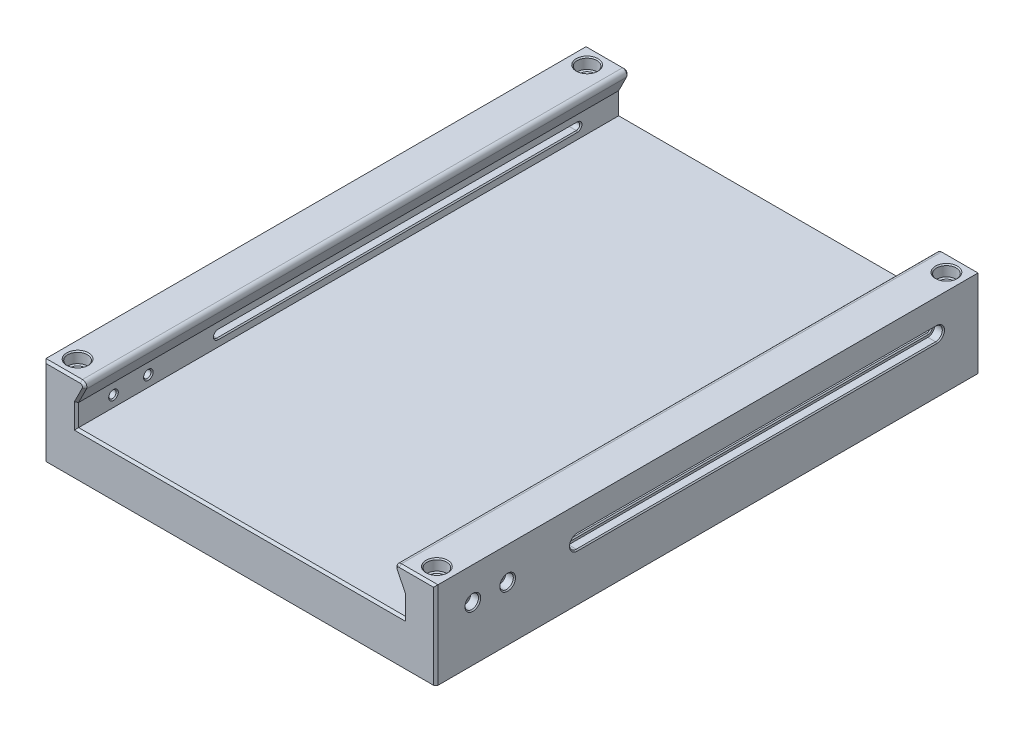
SolidWorks part; units mm, degrees
ref_plane "前视基准面" through (0, 0, 0) normal (0, 0, 1) x (1, 0, 0)
ref_plane "上视基准面" through (0, 0, 0) normal (0, 1, 0) x (1, 0, 0)
ref_plane "右视基准面" through (0, 0, 0) normal (1, 0, 0) x (0, 0, -1)
sketch "草图1" plane through (0, 0, 0) normal (0, 0, 1) x (1, 0, 0)
  line L1 (-90, 10) -> (90, 10)
  line L2 (-90, 10) -> (-90, -10)
  line L3 (-90, -10) -> (90, -10)
  line L4 (90, 10) -> (90, -10)
  line L5 (-90, 10) -> (90, -10) construction
  line L6 (-90, -10) -> (90, 10) construction
  point P0 (0, 0)
  dimension "D1" = 180
  dimension "D2" = 20
extrude "凸台-拉伸1" add sketch "草图1" along normal blind 250
sketch "草图2" plane through (0, 0, 250) normal (0, 0, 1) x (1, 0, 0)
  line L0 (90, 10) -> (-90, 10) construction
  line L1 (-75, 30) -> (-90, 30)
  line L2 (-75, 30) -> (-75, -10)
  line L3 (-75, -10) -> (-90, -10)
  line L4 (-90, 30) -> (-90, -10)
  line L5 (-75, 30) -> (-90, -10) construction
  line L6 (-75, -10) -> (-90, 30) construction
  line L7 (0, 0) -> (0, 83.1513) construction
  line L8 (75, -10) -> (90, 30) construction
  line L9 (75, 30) -> (90, -10) construction
  line L10 (90, 30) -> (90, -10)
  line L11 (75, -10) -> (90, -10)
  line L12 (75, 30) -> (75, -10)
  line L13 (75, 30) -> (90, 30)
  point P0 (-82.5, 10)
  point P15 (82.5, 10)
  dimension "D1" = 15
extrude "凸台-拉伸2" add sketch "草图2" against normal through all
sketch "草图4" plane through (0, 30, 0) normal (0, 1, 0) x (1, 0, 0)
  line L0 (-90, -125) -> (90, -125) construction
  line L1 (-90, 0) -> (-90, -250) construction
  line L2 (90, 0) -> (90, -250) construction
  line L3 (82.5, 0) -> (82.5, -250) construction
  line L4 (90, 0) -> (75, 0) construction
  line L5 (90, -250) -> (75, -250) construction
  line L6 (0, 0) -> (0, -250) construction
  line L7 (75, -250) -> (-75, -250) construction
  circle A30 centre (82.5, -242) radius 2.75
  circle A31 centre (82.5, -8) radius 2.75
  circle A32 centre (-82.5, -242) radius 2.75
  circle A33 centre (-82.5, -8) radius 2.75
  dimension "D1" = 5.5
  dimension "D2" = 8
extrude "切除-拉伸1" cut sketch "草图4" against normal through all
sketch "草图3" plane through (0, 0, 250) normal (0, 0, 1) x (1, 0, 0)
  line L0 (-75, 30) -> (-75, 20)
  line L1 (-75, 10) -> (-75, 30) construction
  line L2 (-75, 20) -> (-70, 30)
  line L3 (-70, 30) -> (-75, 30)
  line L4 (0, 0) -> (0, 81.7607) construction
  line L5 (70, 30) -> (75, 30)
  line L6 (75, 20) -> (70, 30)
  line L7 (75, 30) -> (75, 20)
  dimension "D1" = 5
  dimension "D2" = 10
extrude "凸台-拉伸3" add sketch "草图3" against normal through all
fillet "圆角1" radius 2 2 edges at (70, 30, 125) (-70, 30, 125)
sketch "草图5" plane through (90, 0, 0) normal (1, 0, 0) x (0, 0, -1)
  line L0 (-250, 15) -> (0, 15) construction
  line L1 (-250, -10) -> (-250, 30) construction
  line L2 (0, -10) -> (0, 30) construction
  circle A0 centre (-233, 15) radius 1.7
  circle A1 centre (-217, 15) radius 1.7
  dimension "D3" = 16
  dimension "D4" = 3.4
  dimension "D1" = 5
  dimension "D2" = 17
extrude "切除-拉伸2" cut sketch "草图5" against normal through all
sketch "草图6" plane through (90, 0, 0) normal (1, 0, 0) x (0, 0, -1)
  circle A0 centre (-233, 15) radius 3.1
  circle A1 centre (-217, 15) radius 3.1
  dimension "D1" = 6.2
extrude "切除-拉伸3" cut sketch "草图6" against normal offset from surface (4 mm away) 11 up to face at (75, 15, 234.7)
sketch "草图7" plane through (-90, 0, 0) normal (-1, 0, 0) x (0, 0, 1)
  circle A0 centre (233, 15) radius 3.1
  circle A1 centre (217, 15) radius 3.1
  dimension "D1" = 6.2
extrude "切除-拉伸4" cut sketch "草图7" against normal offset from surface (4 mm away) 11 up to face at (-75, 15, 231.3)
sketch "草图8" plane through (90, 0, 0) normal (1, 0, 0) x (0, 0, -1)
  line L0 (-217, 15) -> (0, 15) construction
  line L1 (0, -10) -> (0, 30) construction
  line L2 (-185, 15) -> (-20, 15) construction
  line L3 (-185, 16.6) -> (-20, 16.6)
  line L4 (-185, 13.4) -> (-20, 13.4)
  arc A0 (-185, 16.6) -> (-185, 13.4) centre (-185, 15) ccw
  arc A1 (-20, 13.4) -> (-20, 16.6) centre (-20, 15) ccw
  point P7 (-102.5, 15)
  dimension "D1" = 3.2
  dimension "D2" = 20
  dimension "D3" = 32
extrude "切除-拉伸5" cut sketch "草图8" against normal through all
sketch "草图9" plane through (90, 0, 0) normal (1, 0, 0) x (0, 0, -1)
  line L0 (-185, 15) -> (-20, 15) construction
  line L1 (-185, 18.1) -> (-20, 18.1)
  line L2 (-185, 11.9) -> (-20, 11.9)
  arc A0 (-185, 18.1) -> (-185, 11.9) centre (-185, 15) ccw
  arc A1 (-20, 11.9) -> (-20, 18.1) centre (-20, 15) ccw
  point P4 (-102.5, 15)
  dimension "D1" = 6.2
extrude "切除-拉伸6" cut sketch "草图9" against normal up to surface (4 mm away) up to face at (86, 15, 220.1)
sketch "草图10" plane through (-90, 0, 0) normal (-1, 0, 0) x (0, 0, 1)
  line L0 (20, 15) -> (185, 15) construction
  line L1 (20, 18.1) -> (185, 18.1)
  line L2 (20, 11.9) -> (185, 11.9)
  arc A0 (20, 18.1) -> (20, 11.9) centre (20, 15) ccw
  arc A1 (185, 11.9) -> (185, 18.1) centre (185, 15) ccw
  point P4 (102.5, 15)
  dimension "D1" = 6.2
extrude "切除-拉伸7" cut sketch "草图10" against normal up to surface (4 mm away) up to face at (-86, 15, 213.9)
sketch "草图11" plane through (0, 30, 0) normal (0, 1, 0) x (1, 0, 0)
  circle A0 centre (-82.5, -8) radius 4.5
  circle A1 centre (82.5, -8) radius 4.5
  circle A2 centre (82.5, -242) radius 4.5
  circle A3 centre (-82.5, -242) radius 4.5
  dimension "D1" = 9
extrude "切除-拉伸8" cut sketch "草图11" against normal blind 5
chamfer "倒角1" distance 1 angle 45 4 edges at (-90, 10, 0) (90, 10, 0) (-90, 10, 250) (90, 10, 250)
chamfer "倒角2" distance 0.5 angle 45 48 edges at (-82.5, 25, 10.75) (-85.25, -10, 8) (82.5, 25, 10.75) (85.25, -10, 8) (75, 15, 234.7) (86, 15, 234.7) (75, 15, 218.7) (86, 15, 218.7) (82.5, 25, 244.75) (79.75, -10, 242) (-82.5, 25, 244.75) (-79.75, -10, 242) (-82.5, 30, 12.5) (82.5, 30, 12.5) (90, 15, 229.9) (90, 15, 213.9) (-90, 15, 236.1) (-90, 15, 220.1) (-86, 15, 215.3) (-86, 15, 231.3) (-90, 18.1, 102.5) (-90, 15, 16.9) (-90, 15, 188.1) (-90, 11.9, 102.5) (-86, 16.6, 102.5) (-86, 15, 18.4) (-86, 15, 186.6) (-86, 13.4, 102.5) (90, 18.1, 102.5) (90, 15, 188.1) (90, 15, 16.9) (90, 11.9, 102.5) (86, 16.6, 102.5) (86, 15, 186.6) (86, 15, 18.4) (86, 13.4, 102.5) (75, 13.4, 102.5) (75, 15, 186.6) (75, 15, 18.4) (75, 16.6, 102.5) (82.5, 30, 246.5) (-82.5, 30, 246.5) (-75, 15, 231.3) (-75, 15, 215.3) (-75, 16.6, 102.5) (-75, 15, 186.6) (-75, 15, 18.4) (-75, 13.4, 102.5)
chamfer "倒角3" distance 1 angle 45 18 edges at (73.2236, 23.5528, 0) (71.5348, 29.0515, 0) (81.118, 30, 0) (75, 15, 0) (0, 10, 0) (-75, 15, 0) (-73.2236, 23.5528, 0) (-71.5348, 29.0515, 0) (-81.118, 30, 0) (-81.118, 30, 250) (-71.5348, 29.0515, 250) (81.118, 30, 250) (71.5348, 29.0515, 250) (73.2236, 23.5528, 250) (75, 15, 250) (-73.2236, 23.5528, 250) (-75, 15, 250) (0, 10, 250)
